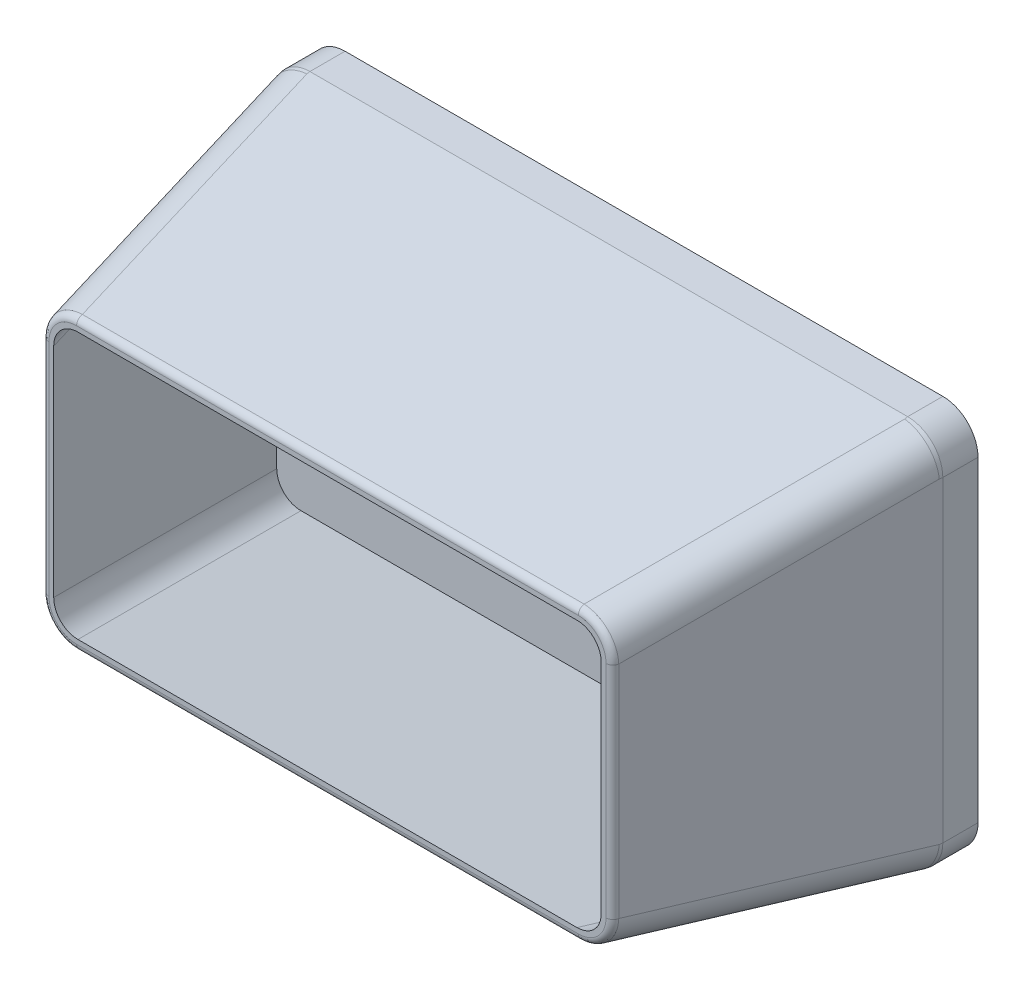
SolidWorks part; units mm, degrees
ref_plane "Front Plane" through (0, 0, 0) normal (0, 0, 1) x (1, 0, 0)
ref_plane "Top Plane" through (0, 0, 0) normal (0, 1, 0) x (1, 0, 0)
ref_plane "Right Plane" through (0, 0, 0) normal (1, 0, 0) x (0, 0, -1)
sketch "Sketch1" plane through (0, 0, 0) normal (0, 0, 1) x (1, 0, 0)
  line L1 (63.75, 41.25) -> (-63.75, 41.25)
  line L2 (71.25, 33.75) -> (71.25, -33.75)
  line L3 (63.75, -41.25) -> (-63.75, -41.25)
  line L4 (-71.25, 33.75) -> (-71.25, -33.75)
  line L5 (71.25, 41.25) -> (-71.25, -41.25) construction
  line L6 (71.25, -41.25) -> (-71.25, 41.25) construction
  arc A0 (-63.75, -41.25) -> (-71.25, -33.75) centre (-63.75, -33.75) cw
  arc A1 (71.25, -33.75) -> (63.75, -41.25) centre (63.75, -33.75) cw
  arc A2 (63.75, 41.25) -> (71.25, 33.75) centre (63.75, 33.75) cw
  arc A3 (-63.75, 41.25) -> (-71.25, 33.75) centre (-63.75, 33.75) ccw
  point P0 (0, 0)
  dimension "D3" = 7.5
  dimension "D1" = 142.5
  dimension "D2" = 82.5
extrude "Boss-Extrude1" add sketch "Sketch1" along normal blind 7.5 contours L1 A3 L4 A0 L3 A1 L2 A2
sketch "Sketch2" plane through (0, 0, 7.5) normal (0, 0, 1) x (1, 0, 0)
  line L4 (63.75, 41.25) -> (-63.75, 41.25)
  line L5 (-71.25, 33.75) -> (-71.25, -33.75)
  line L6 (-63.75, -41.25) -> (63.75, -41.25)
  line L7 (71.25, -33.75) -> (71.25, 33.75)
  line L8 (63.75, 41.25) -> (-63.75, 41.25)
  line L9 (-71.25, 33.75) -> (-71.25, -33.75)
  line L10 (-63.75, -41.25) -> (63.75, -41.25)
  line L11 (71.25, -33.75) -> (71.25, 33.75)
  arc A4 (71.25, 33.75) -> (63.75, 41.25) centre (63.75, 33.75) ccw
  arc A5 (-63.75, 41.25) -> (-71.25, 33.75) centre (-63.75, 33.75) ccw
  arc A6 (-71.25, -33.75) -> (-63.75, -41.25) centre (-63.75, -33.75) ccw
  arc A7 (63.75, -41.25) -> (71.25, -33.75) centre (63.75, -33.75) ccw
  arc A8 (71.25, 33.75) -> (63.75, 41.25) centre (63.75, 33.75) ccw
  arc A9 (-63.75, 41.25) -> (-71.25, 33.75) centre (-63.75, 33.75) ccw
  arc A10 (-71.25, -33.75) -> (-63.75, -41.25) centre (-63.75, -33.75) ccw
  arc A11 (63.75, -41.25) -> (71.25, -33.75) centre (63.75, -33.75) ccw
  dimension "D1" = 0
extrude "Boss-Extrude2" add sketch "Sketch2" along normal blind 60 draft 10 separate body
fillet "Fillet1" radius 7.5 4 edges at (62.2102, -32.2102, 58.7673) (-62.2102, -32.2102, 58.7673) (-62.2102, 32.2102, 58.7673) (62.2102, 32.2102, 58.7673)
shell "Shell1" thickness 2.25 removed face at (0, 0, 67.5)
fillet "Fillet2" radius 1.5 8 edges at (-58.5204, -28.5204, 67.5) (-60.6704, 0, 67.5) (-58.5204, 28.5204, 67.5) (0, 30.6704, 67.5) (58.5204, 28.5204, 67.5) (60.6704, 0, 67.5) (58.5204, -28.5204, 67.5) (0, -30.6704, 67.5)
